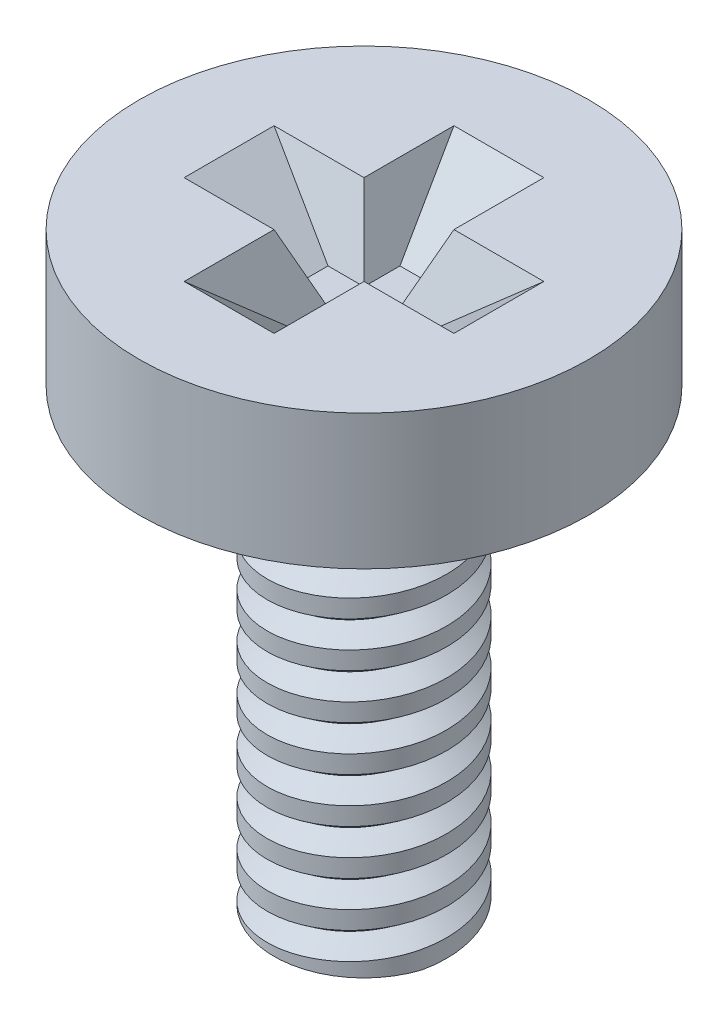
SolidWorks part; units mm, degrees
ref_plane "前视基准面" through (0, 0, 0) normal (0, 0, 1) x (1, 0, 0)
ref_plane "上视基准面" through (0, 0, 0) normal (0, 1, 0) x (1, 0, 0)
ref_plane "右视基准面" through (0, 0, 0) normal (1, 0, 0) x (0, 0, -1)
other "Configuration Table"
sketch "草图1" plane through (0, 0, 0) normal (0, 0, 1) x (1, 0, 0)
  line L0 (0, -33.879) -> (0, 70.1454) construction
  line L1 (0, 32.5) -> (25, 32.5)
  line L2 (25, 32.5) -> (25, 17.5)
  line L3 (25, 17.5) -> (10, 17.5)
  line L4 (10, 17.5) -> (10, -32.5)
  line L5 (10, -32.5) -> (0, -32.5)
  line L6 (0, 32.5) -> (0, -32.5)
  dimension "D1" = 25
  dimension "D2" = 15
  dimension "D3" = 65
  dimension "D4" = 10
  dimension "D5" = 32.5
revolve "旋转1" add sketch "草图1" angle 360 about L0
sketch "草图3" plane through (0, -32.5, 0) normal (0, -1, 0) x (1, 0, 0)
  circle A0 centre (0, 0) radius 10
curve "螺旋线/涡状线1" pitch 5 height 40 radius 10 centre (0, -32.5, 0) axis (0, 1, 0) start towards (0, 0, -1)
sketch "草图5" plane through (0, 0, 0) normal (1, 0, 0) x (0, 0, -1)
  line L0 (10, -31) -> (10, -34)
  line L1 (10, -34) -> (8, -32.5)
  line L2 (8, -32.5) -> (10, -31)
  line L3 (-10, -32.5) -> (10, -32.5) construction
  line L4 (0, 17.5) -> (0, -32.5) construction
  point P8 (10, -32.5)
  dimension "D1" = 2
  dimension "D2" = 3
  dimension "D3" = 10
sweep "切除-扫描1" cut profiles "草图5" path "螺旋线/涡状线1" align with end faces yes
sketch "草图6" plane through (0, 32.5, 0) normal (0, 1, 0) x (1, 0, 0)
  line L0 (0, 26.0846) -> (0, -28.3391) construction
  line L1 (-5, 15) -> (5, 15)
  line L2 (5, 15) -> (5, 5)
  line L3 (5, 5) -> (15, 5)
  line L4 (15, 5) -> (15, -5)
  line L5 (-39.093, 0) -> (27.4147, 0) construction
  line L6 (-15, 5) -> (-15, -5)
  line L7 (-5, 5) -> (-15, 5)
  line L8 (-5, 15) -> (-5, 5)
  line L9 (-5, -15) -> (-5, -5)
  line L10 (-5, -5) -> (-15, -5)
  line L11 (5, -5) -> (15, -5)
  line L12 (5, -15) -> (5, -5)
  line L13 (-5, -15) -> (5, -15)
  point P15 (0, 15)
  point P18 (-15, 0)
  point P19 (15, 0)
  point P21 (0, -15)
  dimension "D1" = 5
  dimension "D2" = 10
ref_plane "基准面1" through (0, 25, 0) normal (0, 1, 0) x (1, 0, 0)
sketch "草图7" plane through (0, 25, 0) normal (0, 1, 0) x (1, 0, 0)
  line L0 (-2, 6) -> (2, 6)
  line L1 (0, 26.0846) -> (0, -28.3391) construction
  line L2 (2, 6) -> (2, 2)
  line L3 (2, 2) -> (6, 2)
  line L4 (6, 2) -> (6, -2)
  line L5 (-39.093, 0) -> (27.4147, 0) construction
  line L6 (0, 3.7338) -> (0, -1.1755) construction
  line L7 (-3.0257, 0) -> (2.949, 0) construction
  line L8 (-6, 2) -> (-6, -2)
  line L9 (-2, 2) -> (-6, 2)
  line L10 (-2, 6) -> (-2, 2)
  line L11 (-2, -6) -> (-2, -2)
  line L12 (-2, -2) -> (-6, -2)
  line L13 (2, -2) -> (6, -2)
  line L14 (2, -6) -> (2, -2)
  line L15 (-2, -6) -> (2, -6)
  point P16 (0, 6)
  point P18 (6, 0)
  point P19 (-6, 0)
  point P23 (0, -6)
  dimension "D1" = 2
  dimension "D2" = 4
loft "切除-放样1" cut profiles "草图6", "草图7" connector at (-5, 32.5, -15) connector at (-2, 25, -6)
